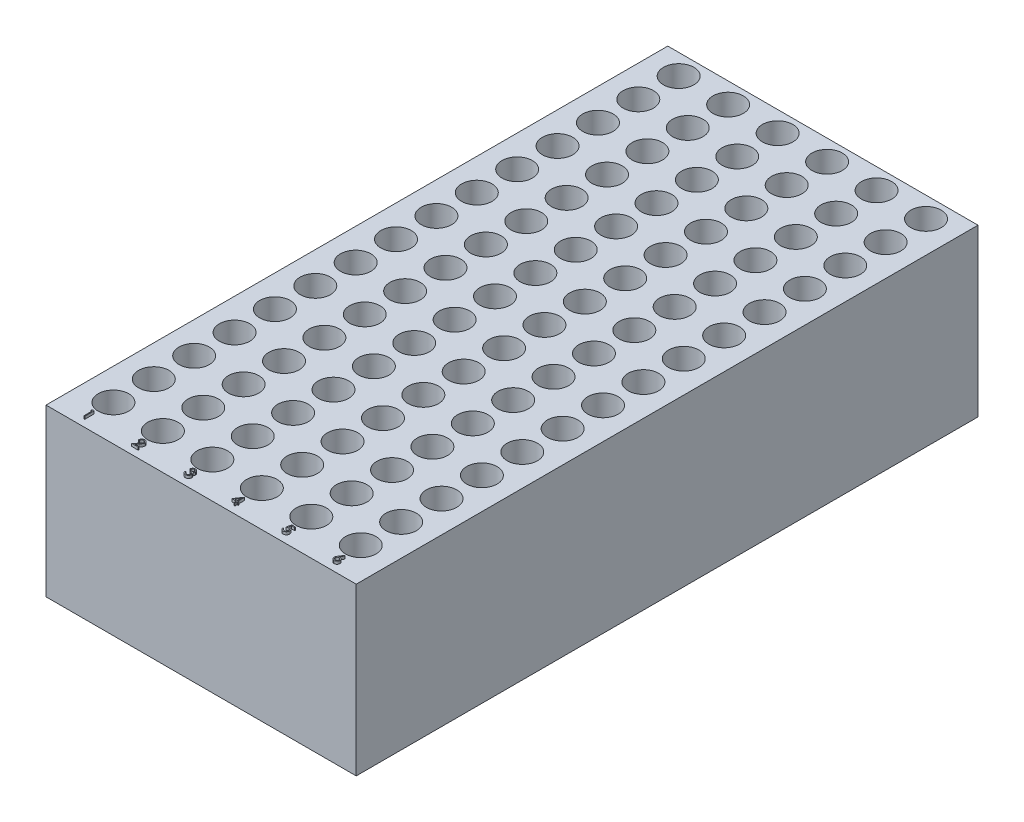
SolidWorks part; units mm, degrees
ref_plane "Front Plane" through (0, 0, 0) normal (0, 0, 1) x (1, 0, 0)
ref_plane "Top Plane" through (0, 0, 0) normal (0, 1, 0) x (1, 0, 0)
ref_plane "Right Plane" through (0, 0, 0) normal (1, 0, 0) x (0, 0, -1)
sketch "Sketch1" plane through (0, 0, 0) normal (0, 1, 0) x (1, 0, 0)
  line L0 (-45.9468, 107.87) -> (-57.625, 107.87) construction
  line L1 (57.625, -115.5) -> (-57.625, -115.5)
  line L2 (57.625, -115.5) -> (57.625, 115.5)
  line L3 (57.625, 115.5) -> (-57.625, 115.5)
  line L4 (-57.625, -115.5) -> (-57.625, 115.5)
  line L5 (57.625, -115.5) -> (-57.625, 115.5) construction
  line L6 (57.625, 115.5) -> (-57.625, -115.5) construction
  line L7 (45.9468, 107.87) -> (57.625, 107.87) construction
  line L8 (-45.9468, 107.87) -> (-45.9468, 115.5) construction
  line L10 (-45.9468, -87.13) -> (-57.625, -87.13) construction
  circle A0 centre (-45.9468, 107.87) radius 5.65
  circle A1 centre (-27.5681, 107.87) radius 5.65
  circle A2 centre (-9.1894, 107.87) radius 5.65
  circle A3 centre (9.1894, 107.87) radius 5.65
  circle A4 centre (27.5681, 107.87) radius 5.65
  circle A5 centre (45.9468, 107.87) radius 5.65
  circle A6 centre (-45.9468, 92.87) radius 5.65
  circle A7 centre (-27.5681, 92.87) radius 5.65
  circle A8 centre (-9.1894, 92.87) radius 5.65
  circle A9 centre (9.1894, 92.87) radius 5.65
  circle A10 centre (27.5681, 92.87) radius 5.65
  circle A11 centre (45.9468, 92.87) radius 5.65
  circle A12 centre (-45.9468, 77.87) radius 5.65
  circle A13 centre (-27.5681, 77.87) radius 5.65
  circle A14 centre (-9.1894, 77.87) radius 5.65
  circle A15 centre (9.1894, 77.87) radius 5.65
  circle A16 centre (27.5681, 77.87) radius 5.65
  circle A17 centre (45.9468, 77.87) radius 5.65
  circle A18 centre (-45.9468, 62.87) radius 5.65
  circle A19 centre (-27.5681, 62.87) radius 5.65
  circle A20 centre (-9.1894, 62.87) radius 5.65
  circle A21 centre (9.1894, 62.87) radius 5.65
  circle A22 centre (27.5681, 62.87) radius 5.65
  circle A23 centre (45.9468, 62.87) radius 5.65
  circle A24 centre (-45.9468, 47.87) radius 5.65
  circle A25 centre (-27.5681, 47.87) radius 5.65
  circle A26 centre (-9.1894, 47.87) radius 5.65
  circle A27 centre (9.1894, 47.87) radius 5.65
  circle A28 centre (27.5681, 47.87) radius 5.65
  circle A29 centre (45.9468, 47.87) radius 5.65
  circle A30 centre (-45.9468, 32.87) radius 5.65
  circle A31 centre (-27.5681, 32.87) radius 5.65
  circle A32 centre (-9.1894, 32.87) radius 5.65
  circle A33 centre (9.1894, 32.87) radius 5.65
  circle A34 centre (27.5681, 32.87) radius 5.65
  circle A35 centre (45.9468, 32.87) radius 5.65
  circle A36 centre (-45.9468, 17.87) radius 5.65
  circle A37 centre (-27.5681, 17.87) radius 5.65
  circle A38 centre (-9.1894, 17.87) radius 5.65
  circle A39 centre (9.1894, 17.87) radius 5.65
  circle A40 centre (27.5681, 17.87) radius 5.65
  circle A41 centre (45.9468, 17.87) radius 5.65
  circle A42 centre (-45.9468, 2.87) radius 5.65
  circle A43 centre (-27.5681, 2.87) radius 5.65
  circle A44 centre (-9.1894, 2.87) radius 5.65
  circle A45 centre (9.1894, 2.87) radius 5.65
  circle A46 centre (27.5681, 2.87) radius 5.65
  circle A47 centre (45.9468, 2.87) radius 5.65
  circle A48 centre (-45.9468, -12.13) radius 5.65
  circle A49 centre (-27.5681, -12.13) radius 5.65
  circle A50 centre (-9.1894, -12.13) radius 5.65
  circle A51 centre (9.1894, -12.13) radius 5.65
  circle A52 centre (27.5681, -12.13) radius 5.65
  circle A53 centre (45.9468, -12.13) radius 5.65
  circle A54 centre (-45.9468, -27.13) radius 5.65
  circle A55 centre (-27.5681, -27.13) radius 5.65
  circle A56 centre (-9.1894, -27.13) radius 5.65
  circle A57 centre (9.1894, -27.13) radius 5.65
  circle A58 centre (27.5681, -27.13) radius 5.65
  circle A59 centre (45.9468, -27.13) radius 5.65
  circle A60 centre (-45.9468, -42.13) radius 5.65
  circle A61 centre (-27.5681, -42.13) radius 5.65
  circle A62 centre (-9.1894, -42.13) radius 5.65
  circle A63 centre (9.1894, -42.13) radius 5.65
  circle A64 centre (27.5681, -42.13) radius 5.65
  circle A65 centre (45.9468, -42.13) radius 5.65
  circle A66 centre (-45.9468, -57.13) radius 5.65
  circle A67 centre (-27.5681, -57.13) radius 5.65
  circle A68 centre (-9.1894, -57.13) radius 5.65
  circle A69 centre (9.1894, -57.13) radius 5.65
  circle A70 centre (27.5681, -57.13) radius 5.65
  circle A71 centre (45.9468, -57.13) radius 5.65
  circle A72 centre (-45.9468, -72.13) radius 5.65
  circle A73 centre (-27.5681, -72.13) radius 5.65
  circle A74 centre (-9.1894, -72.13) radius 5.65
  circle A75 centre (9.1894, -72.13) radius 5.65
  circle A76 centre (27.5681, -72.13) radius 5.65
  circle A77 centre (45.9468, -72.13) radius 5.65
  circle A78 centre (-45.9468, -87.13) radius 5.65
  circle A79 centre (-27.5681, -87.13) radius 5.65
  circle A80 centre (-9.1894, -87.13) radius 5.65
  circle A81 centre (9.1894, -87.13) radius 5.65
  circle A82 centre (27.5681, -87.13) radius 5.65
  circle A83 centre (45.9468, -87.13) radius 5.65
  circle A90 centre (-45.9468, -102.13) radius 5.65
  circle A91 centre (-27.5681, -102.13) radius 5.65
  circle A92 centre (-9.1894, -102.13) radius 5.65
  circle A93 centre (9.1894, -102.13) radius 5.65
  circle A94 centre (27.5681, -102.13) radius 5.65
  circle A95 centre (45.9468, -102.13) radius 5.65
  point P0 (0, 0)
  dimension "D1" = 11.3
  dimension "D5" = 7.63
  dimension "D7" = 231
  dimension "D8" = 15
  dimension "D9" = 115.25
  dimension "D2" = 6
  dimension "D6" = 15
extrude "Boss-Extrude1" add sketch "Sketch1" along normal blind 51.7
sketch "Sketch2" plane through (0, 0, 0) normal (0, -1, 0) x (1, 0, 0)
  line L1 (57.625, -115.5) -> (-57.625, -115.5)
  line L2 (57.625, -115.5) -> (57.625, 115.5)
  line L3 (57.625, 115.5) -> (-57.625, 115.5)
  line L4 (-57.625, -115.5) -> (-57.625, 115.5)
  line L5 (57.625, -115.5) -> (-57.625, 115.5) construction
  line L6 (57.625, 115.5) -> (-57.625, -115.5) construction
  point P0 (0, 0)
extrude "Boss-Extrude2" add sketch "Sketch2" along normal blind 10
sketch "Sketch3" plane through (0, 0, 0) normal (0, 1, 0) x (1, 0, 0)
  circle A0 centre (-45.9468, -102.13) radius 4.225
  circle A1 centre (-27.5668, -102.13) radius 4.225
  circle A2 centre (-9.1868, -102.13) radius 4.225
  circle A3 centre (9.1932, -102.13) radius 4.225
  circle A4 centre (27.5732, -102.13) radius 4.225
  circle A5 centre (45.9532, -102.13) radius 4.225
  circle A6 centre (-27.5668, -87.13) radius 4.225
  circle A7 centre (-9.1868, -87.13) radius 4.225
  circle A8 centre (9.1932, -87.13) radius 4.225
  circle A9 centre (27.5732, -87.13) radius 4.225
  circle A10 centre (45.9532, -87.13) radius 4.225
  circle A11 centre (-27.5668, -72.13) radius 4.225
  circle A12 centre (-9.1868, -72.13) radius 4.225
  circle A13 centre (9.1932, -72.13) radius 4.225
  circle A14 centre (27.5732, -72.13) radius 4.225
  circle A15 centre (45.9532, -72.13) radius 4.225
  circle A16 centre (-27.5668, -57.13) radius 4.225
  circle A17 centre (-9.1868, -57.13) radius 4.225
  circle A18 centre (9.1932, -57.13) radius 4.225
  circle A19 centre (27.5732, -57.13) radius 4.225
  circle A20 centre (45.9532, -57.13) radius 4.225
  circle A21 centre (-27.5668, -42.13) radius 4.225
  circle A22 centre (-9.1868, -42.13) radius 4.225
  circle A23 centre (9.1932, -42.13) radius 4.225
  circle A24 centre (27.5732, -42.13) radius 4.225
  circle A25 centre (45.9532, -42.13) radius 4.225
  circle A26 centre (-27.5668, -27.13) radius 4.225
  circle A27 centre (-9.1868, -27.13) radius 4.225
  circle A28 centre (9.1932, -27.13) radius 4.225
  circle A29 centre (27.5732, -27.13) radius 4.225
  circle A30 centre (45.9532, -27.13) radius 4.225
  circle A31 centre (-27.5668, -12.13) radius 4.225
  circle A32 centre (-9.1868, -12.13) radius 4.225
  circle A33 centre (9.1932, -12.13) radius 4.225
  circle A34 centre (27.5732, -12.13) radius 4.225
  circle A35 centre (45.9532, -12.13) radius 4.225
  circle A36 centre (-27.5668, 2.87) radius 4.225
  circle A37 centre (-9.1868, 2.87) radius 4.225
  circle A38 centre (9.1932, 2.87) radius 4.225
  circle A39 centre (27.5732, 2.87) radius 4.225
  circle A40 centre (45.9532, 2.87) radius 4.225
  circle A41 centre (-27.5668, 17.87) radius 4.225
  circle A42 centre (-9.1868, 17.87) radius 4.225
  circle A43 centre (9.1932, 17.87) radius 4.225
  circle A44 centre (27.5732, 17.87) radius 4.225
  circle A45 centre (45.9532, 17.87) radius 4.225
  circle A46 centre (-27.5668, 32.87) radius 4.225
  circle A47 centre (-9.1868, 32.87) radius 4.225
  circle A48 centre (9.1932, 32.87) radius 4.225
  circle A49 centre (27.5732, 32.87) radius 4.225
  circle A50 centre (45.9532, 32.87) radius 4.225
  circle A51 centre (-27.5668, 47.87) radius 4.225
  circle A52 centre (-9.1868, 47.87) radius 4.225
  circle A53 centre (9.1932, 47.87) radius 4.225
  circle A54 centre (27.5732, 47.87) radius 4.225
  circle A55 centre (45.9532, 47.87) radius 4.225
  circle A56 centre (-27.5668, 62.87) radius 4.225
  circle A57 centre (-9.1868, 62.87) radius 4.225
  circle A58 centre (9.1932, 62.87) radius 4.225
  circle A59 centre (27.5732, 62.87) radius 4.225
  circle A60 centre (45.9532, 62.87) radius 4.225
  circle A61 centre (-27.5668, 77.87) radius 4.225
  circle A62 centre (-9.1868, 77.87) radius 4.225
  circle A63 centre (9.1932, 77.87) radius 4.225
  circle A64 centre (27.5732, 77.87) radius 4.225
  circle A65 centre (45.9532, 77.87) radius 4.225
  circle A66 centre (-27.5668, 92.87) radius 4.225
  circle A67 centre (-9.1868, 92.87) radius 4.225
  circle A68 centre (9.1932, 92.87) radius 4.225
  circle A69 centre (27.5732, 92.87) radius 4.225
  circle A70 centre (45.9532, 92.87) radius 4.225
  circle A71 centre (-27.5668, 107.87) radius 4.225
  circle A72 centre (-9.1868, 107.87) radius 4.225
  circle A73 centre (9.1932, 107.87) radius 4.225
  circle A74 centre (27.5732, 107.87) radius 4.225
  circle A75 centre (45.9532, 107.87) radius 4.225
  circle A76 centre (-45.9468, -87.13) radius 4.225
  circle A77 centre (-45.9468, -72.13) radius 4.225
  circle A78 centre (-45.9468, -57.13) radius 4.225
  circle A79 centre (-45.9468, -42.13) radius 4.225
  circle A80 centre (-45.9468, -27.13) radius 4.225
  circle A81 centre (-45.9468, -12.13) radius 4.225
  circle A82 centre (-45.9468, 2.87) radius 4.225
  circle A83 centre (-45.9468, 17.87) radius 4.225
  circle A84 centre (-45.9468, 32.87) radius 4.225
  circle A85 centre (-45.9468, 47.87) radius 4.225
  circle A86 centre (-45.9468, 62.87) radius 4.225
  circle A87 centre (-45.9468, 77.87) radius 4.225
  circle A88 centre (-45.9468, 92.87) radius 4.225
  circle A89 centre (-45.9468, 107.87) radius 4.225
  circle A90 centre (-45.9468, -102.13) radius 5.65
  circle A91 centre (-45.9468, -102.13) radius 5.65 construction
  circle A92 centre (-27.5668, -102.13) radius 5.65
  circle A93 centre (-9.1868, -102.13) radius 5.65
  circle A94 centre (9.1932, -102.13) radius 5.65
  circle A95 centre (27.5732, -102.13) radius 5.65
  circle A96 centre (45.9532, -102.13) radius 5.65
  circle A97 centre (-27.5668, -87.13) radius 5.65
  circle A98 centre (-9.1868, -87.13) radius 5.65
  circle A99 centre (9.1932, -87.13) radius 5.65
  circle A100 centre (27.5732, -87.13) radius 5.65
  circle A101 centre (45.9532, -87.13) radius 5.65
  circle A102 centre (-27.5668, -72.13) radius 5.65
  circle A103 centre (-9.1868, -72.13) radius 5.65
  circle A104 centre (9.1932, -72.13) radius 5.65
  circle A105 centre (27.5732, -72.13) radius 5.65
  circle A106 centre (45.9532, -72.13) radius 5.65
  circle A107 centre (-27.5668, -57.13) radius 5.65
  circle A108 centre (-9.1868, -57.13) radius 5.65
  circle A109 centre (9.1932, -57.13) radius 5.65
  circle A110 centre (27.5732, -57.13) radius 5.65
  circle A111 centre (45.9532, -57.13) radius 5.65
  circle A112 centre (-27.5668, -42.13) radius 5.65
  circle A113 centre (-9.1868, -42.13) radius 5.65
  circle A114 centre (9.1932, -42.13) radius 5.65
  circle A115 centre (27.5732, -42.13) radius 5.65
  circle A116 centre (45.9532, -42.13) radius 5.65
  circle A117 centre (-27.5668, -27.13) radius 5.65
  circle A118 centre (-9.1868, -27.13) radius 5.65
  circle A119 centre (9.1932, -27.13) radius 5.65
  circle A120 centre (27.5732, -27.13) radius 5.65
  circle A121 centre (45.9532, -27.13) radius 5.65
  circle A122 centre (-27.5668, -12.13) radius 5.65
  circle A123 centre (-9.1868, -12.13) radius 5.65
  circle A124 centre (9.1932, -12.13) radius 5.65
  circle A125 centre (27.5732, -12.13) radius 5.65
  circle A126 centre (45.9532, -12.13) radius 5.65
  circle A127 centre (-27.5668, 2.87) radius 5.65
  circle A128 centre (-9.1868, 2.87) radius 5.65
  circle A129 centre (9.1932, 2.87) radius 5.65
  circle A130 centre (27.5732, 2.87) radius 5.65
  circle A131 centre (45.9532, 2.87) radius 5.65
  circle A132 centre (-27.5668, 17.87) radius 5.65
  circle A133 centre (-9.1868, 17.87) radius 5.65
  circle A134 centre (9.1932, 17.87) radius 5.65
  circle A135 centre (27.5732, 17.87) radius 5.65
  circle A136 centre (45.9532, 17.87) radius 5.65
  circle A137 centre (-27.5668, 32.87) radius 5.65
  circle A138 centre (-9.1868, 32.87) radius 5.65
  circle A139 centre (9.1932, 32.87) radius 5.65
  circle A140 centre (27.5732, 32.87) radius 5.65
  circle A141 centre (45.9532, 32.87) radius 5.65
  circle A142 centre (-27.5668, 47.87) radius 5.65
  circle A143 centre (-9.1868, 47.87) radius 5.65
  circle A144 centre (9.1932, 47.87) radius 5.65
  circle A145 centre (27.5732, 47.87) radius 5.65
  circle A146 centre (45.9532, 47.87) radius 5.65
  circle A147 centre (-27.5668, 62.87) radius 5.65
  circle A148 centre (-9.1868, 62.87) radius 5.65
  circle A149 centre (9.1932, 62.87) radius 5.65
  circle A150 centre (27.5732, 62.87) radius 5.65
  circle A151 centre (45.9532, 62.87) radius 5.65
  circle A152 centre (-27.5668, 77.87) radius 5.65
  circle A153 centre (-9.1868, 77.87) radius 5.65
  circle A154 centre (9.1932, 77.87) radius 5.65
  circle A155 centre (27.5732, 77.87) radius 5.65
  circle A156 centre (45.9532, 77.87) radius 5.65
  circle A157 centre (-27.5668, 92.87) radius 5.65
  circle A158 centre (-9.1868, 92.87) radius 5.65
  circle A159 centre (9.1932, 92.87) radius 5.65
  circle A160 centre (27.5732, 92.87) radius 5.65
  circle A161 centre (45.9532, 92.87) radius 5.65
  circle A162 centre (-27.5668, 107.87) radius 5.65
  circle A163 centre (-9.1868, 107.87) radius 5.65
  circle A164 centre (9.1932, 107.87) radius 5.65
  circle A165 centre (27.5732, 107.87) radius 5.65
  circle A166 centre (45.9532, 107.87) radius 5.65
  circle A167 centre (-45.9468, -87.13) radius 5.65
  circle A168 centre (-45.9468, -72.13) radius 5.65
  circle A169 centre (-45.9468, -57.13) radius 5.65
  circle A170 centre (-45.9468, -42.13) radius 5.65
  circle A171 centre (-45.9468, -27.13) radius 5.65
  circle A172 centre (-45.9468, -12.13) radius 5.65
  circle A173 centre (-45.9468, 2.87) radius 5.65
  circle A174 centre (-45.9468, 17.87) radius 5.65
  circle A175 centre (-45.9468, 32.87) radius 5.65
  circle A176 centre (-45.9468, 47.87) radius 5.65
  circle A177 centre (-45.9468, 62.87) radius 5.65
  circle A178 centre (-45.9468, 77.87) radius 5.65
  circle A179 centre (-45.9468, 92.87) radius 5.65
  circle A180 centre (-45.9468, 107.87) radius 5.65
  dimension "D1" = 8.45
  dimension "D6" = 15
  dimension "D8" = 15
  dimension "D9" = 18.38
  dimension "D4" = 15
  dimension "D5" = 18.38
  dimension "D2" = 6
  dimension "D3" = 15
  dimension "D7" = 6
extrude "Boss-Extrude4" add sketch "Sketch3" along normal blind 30
sketch "Sketch5" plane through (0, 51.7, 0) normal (0, 1, 0) x (1, 0, 0)
  text T0 "1            2            3           4            5            6"
extrude "Boss-Extrude5" add sketch "Sketch5" along normal blind 1
